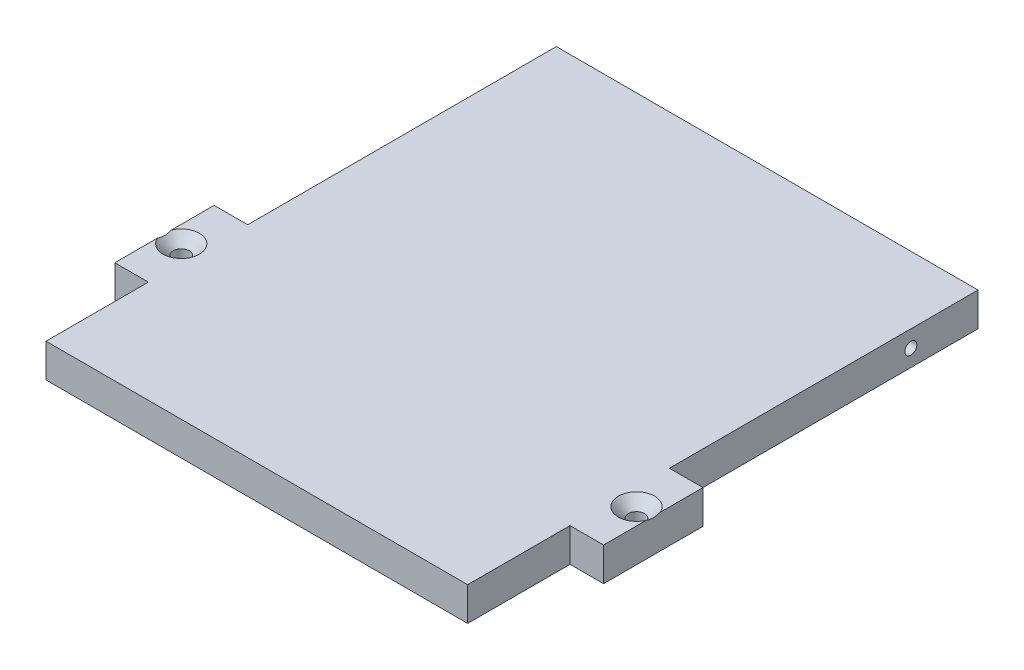
SolidWorks part; units mm, degrees
ref_plane "Front Plane" through (0, 0, 0) normal (0, 0, 1) x (1, 0, 0)
ref_plane "Top Plane" through (0, 0, 0) normal (0, 1, 0) x (1, 0, 0)
ref_plane "Right Plane" through (0, 0, 0) normal (1, 0, 0) x (0, 0, -1)
sketch "Sketch1" plane through (0, 0, 0) normal (0, 1, 0) x (1, 0, 0)
  line L0 (39.6884, 96.2364) -> (39.6884, 76.2)
  line L1 (39.6884, 96.2364) -> (-40.0676, 96.2364)
  line L2 (-0.1896, 96.2364) -> (-0.1896, -0.2836) construction
  line L3 (-40.0676, -0.2836) -> (39.6884, -0.2836)
  line L4 (42.8634, 37.8672) -> (42.8634, 19.0712) construction
  line L5 (46.0384, 19.0712) -> (39.6884, 19.0712)
  line L6 (39.6884, 37.8672) -> (46.0384, 37.8672)
  line L7 (46.0384, 19.0712) -> (46.0384, 37.8672)
  line L8 (39.6884, 19.0712) -> (39.6884, -0.2836)
  line L9 (39.6884, 57.404) -> (39.6884, 76.2)
  line L10 (-40.0676, 57.404) -> (-40.0676, 76.2)
  line L11 (39.6884, 57.404) -> (39.6884, 37.8672)
  line L12 (46.0384, 28.4692) -> (-61.3595, 28.4692) construction
  line L13 (39.6884, 47.6356) -> (-0.1896, 47.9764) construction
  line L14 (-43.2426, 37.8672) -> (-43.2426, 19.0712) construction
  line L15 (39.6884, 19.0712) -> (-46.4176, 19.0712) construction
  line L16 (-40.0676, 57.404) -> (-40.0676, 37.8672)
  line L17 (-40.0676, 37.8672) -> (39.6884, 37.8672) construction
  line L19 (-40.0676, 19.0712) -> (-40.0676, -0.2836)
  line L20 (-46.4176, 19.0712) -> (-46.4176, 37.8672)
  line L21 (-40.0676, 37.8672) -> (-46.4176, 37.8672)
  line L22 (-46.4176, 19.0712) -> (-40.0676, 19.0712)
  line L23 (-40.0676, 96.2364) -> (-40.0676, 76.2)
  circle A0 centre (42.8634, 28.4692) radius 1.524
  circle A3 centre (-43.2426, 28.4692) radius 1.524
  dimension "D4" = 3.048
  dimension "D1" = 39.878
  dimension "D3" = 18.796
  dimension "D6" = 38.1508
  dimension "D7" = 96.52
extrude "Boss-Extrude1" add sketch "Sketch1" along normal blind 6.35 contours L20 A3 L22 L19 L3 L8 L5 L7 A0 L6 L11 L0 L1 L23 L16 L21 region at (-0.1896, 0, -47.4246)
chamfer "Chamfer1" distance 1.905 angle 45 2 edges at (42.8634, 6.35, -26.9452) (-43.2426, 6.35, -26.9452)
sketch "Sketch2" plane through (-40.0676, 0, 0) normal (-1, 0, 0) x (0, 0, 1)
  line L0 (-96.2364, 6.35) -> (-96.2364, 0) construction
  line L1 (-96.2364, 3.175) -> (-55.4063, 3.175) construction
  circle A0 centre (-83.5364, 3.175) radius 1.1303
  dimension "D1" = 2.2606
  dimension "D2" = 12.7
extrude "Cut-Extrude1" cut sketch "Sketch2" against normal blind 12.7
mirror "Mirror5" about plane through (0, 0, 0) normal (1, 0, 0) of "Cut-Extrude1"
